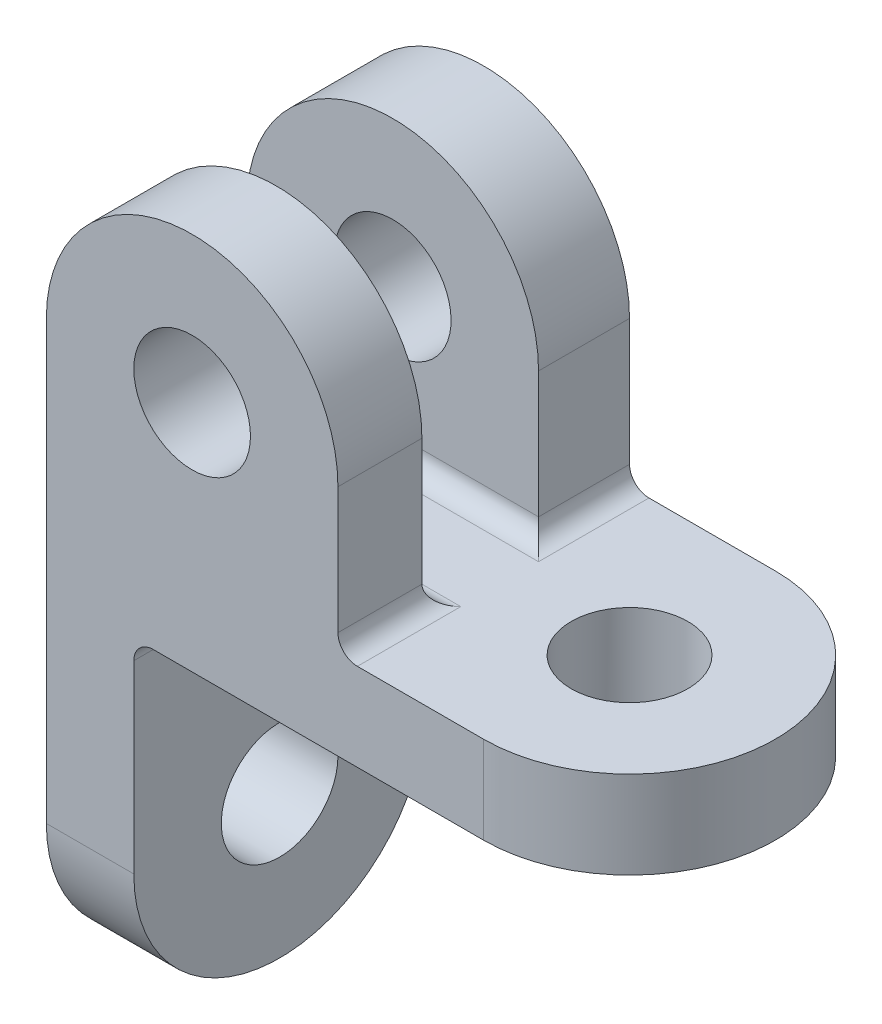
SolidWorks part; units mm, degrees
ref_plane "Front Plane" through (0, 0, 0) normal (0, 0, 1) x (1, 0, 0)
ref_plane "Top Plane" through (0, 0, 0) normal (0, 1, 0) x (1, 0, 0)
ref_plane "Right Plane" through (0, 0, 0) normal (1, 0, 0) x (0, 0, -1)
sketch "Sketch1" plane through (0, 0, 0) normal (0, 0, 1) x (1, 0, 0)
  line L0 (1000, 0) -> (0, 0) construction
  line L1 (0, 0) -> (0, 42029.9863) construction
  line L2 (15, 15) -> (15, 0)
  line L3 (15, 0) -> (45, 0)
  line L4 (45, 0) -> (45, -9)
  line L5 (45, -9) -> (7.1553, -9)
  line L6 (-15, 15) -> (-15, -45)
  line L7 (-15, -45) -> (-6, -45)
  line L8 (-6, -45) -> (-6, -9)
  line L9 (-6, -9) -> (7.1553, -9)
  line L10 (-15, 0) -> (-42029.9863, 0) construction
  circle A0 centre (0, 15) radius 6
  arc A1 (15, 15) -> (-15, 15) centre (0, 15) ccw
  dimension "D1" = 12
  dimension "D2" = 30
  dimension "D3" = 15
  dimension "D4" = 60
  dimension "D5" = 9
  dimension "D6" = 9
  dimension "D7" = 30
extrude "Boss-Extrude1" add sketch "Sketch1" along normal blind 30
fillet "Fillet2" 2 edges at (45, -4.5, 30) (45, -4.5, 0) type full round first side face at (9.75, -7.875, 30) second side face at (9.75, -7.875, 0) middle face at (45, -4.5, 15)
fillet "Fillet3" 2 edges at (-10.5, -45, 30) (-10.5, -45, 0) type full round first side face at (6, -7.875, 30) second side face at (6, -7.875, 0) middle face at (-10.5, -45, 15)
sketch "Sketch2" plane through (15, 0, 0) normal (1, 0, 0) x (0, 0, -1)
  line L0 (-9.36, 0) -> (-21.36, 0)
  line L2 (0, 0) -> (-30, 0) construction
  line L3 (-21.36, 0) -> (-21.36, 40.9708)
  line L4 (-21.36, 40.9708) -> (-9.36, 40.9708)
  line L5 (-9.36, 40.9708) -> (-9.36, 0)
  point P3 (-15.36, 0)
  dimension "D1" = 12
extrude "Cut-Extrude1" cut sketch "Sketch2" against normal blind 59 and the other way blind 10
hole_wizard "Ø12.0mm Dowel Hole1" positions "3DSketch1" profile "Sketch5" hole size "Ø12.0" standard "ANSI Metric"
sketch3d "3DSketch1"
  line L0 (30, -9, 15) -> (30, 0, 15) construction
  line L1 (-15, -30, 15) -> (-6, -30, 15) construction
  point P0 (30, 0, 15)
  point P4 (-6, -30, 15)
sketch "Sketch5" plane through (30, 0, 15) normal (1, 0, 0) x (0, 0, 1)
  line L0 (0, 0) -> (0, 13.6052)
  line L1 (0, 13.6052) -> (6, 10)
  line L2 (6, 10) -> (6, 0)
  line L5 (6, 0) -> (0, 0)
  line L10 (0, 13.6052) -> (-6, 10) construction
  line L11 (0, -6.35) -> (0, 107.95) construction
  dimension "Hole Dia." = 12
  dimension "Hole Depth" = 10
  dimension "Drill Angle" = 118
fillet "Fillet4" radius 2 5 edges at (-6, -9, 15) (0, 0, 9.36) (0, 0, 21.36) (15, 0, 4.68) (15, 0, 25.68)
